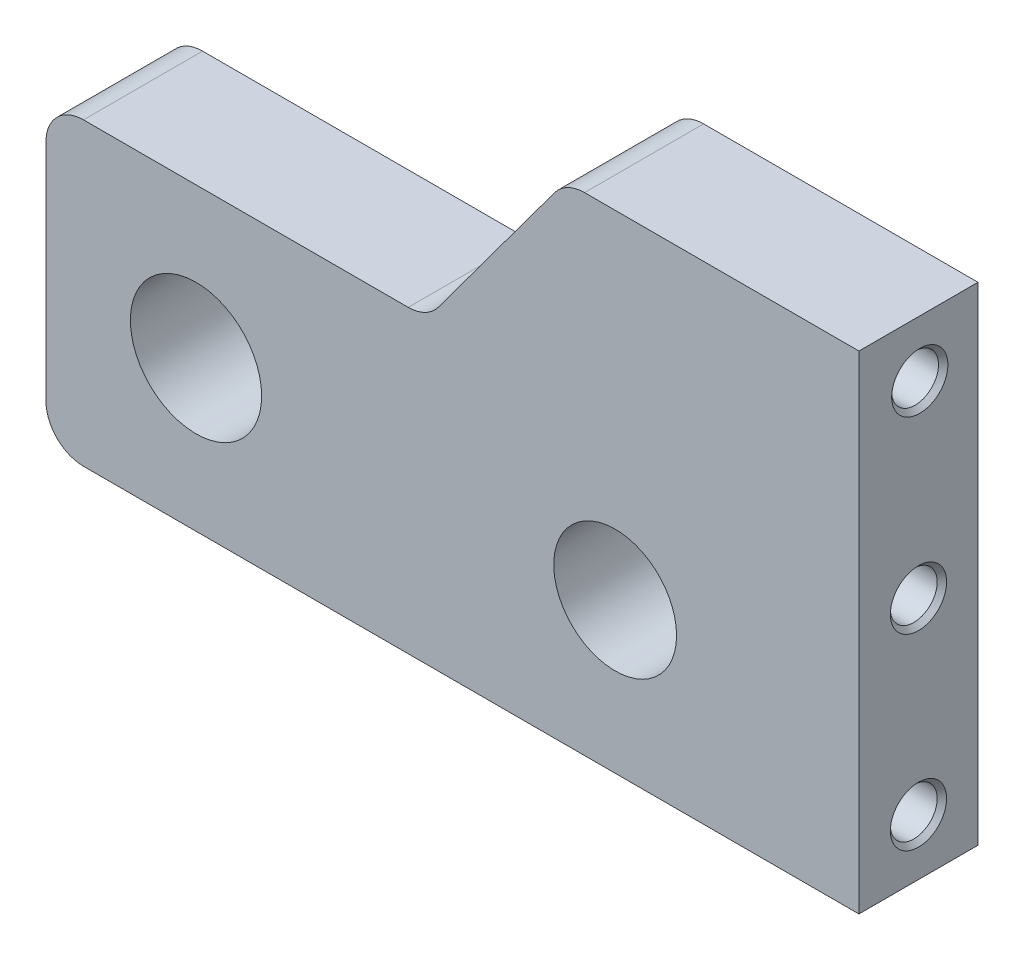
SolidWorks part; units mm, degrees
ref_plane "Front Plane" through (0, 0, 0) normal (0, 0, 1) x (1, 0, 0)
ref_plane "Top Plane" through (0, 0, 0) normal (0, 1, 0) x (1, 0, 0)
ref_plane "Right Plane" through (0, 0, 0) normal (1, 0, 0) x (0, 0, -1)
sketch "Sketch1" plane through (0, 0, 0) normal (0, 0, 1) x (1, 0, 0)
  line L0 (43.352, 8) -> (0, 8) construction
  line L1 (0, 0) -> (43.352, 0)
  line L2 (0, 0) -> (0, 16)
  line L3 (0, 16) -> (43.352, 16)
  line L4 (43.352, 0) -> (43.352, 16)
  circle A0 centre (8, 8) radius 3.5
  circle A1 centre (30.352, 8) radius 3.275
  dimension "D5" = 7
  dimension "D6" = 6.55
  dimension "D1" = 13
  dimension "D2" = 16
  dimension "D3" = 22.352
  dimension "D4" = 8
extrude "Boss-Extrude1" add sketch "Sketch1" along normal blind 6.35 contours L3 L4 L1 L2
extrude "Cut-Extrude1" cut sketch "Sketch1<6>" along normal blind 6.35 contours A0 L0 | L0 A0 | A1 region at (8, 6.5146, 0) region at (8, 9.4854, 0)
sketch "Sketch1<6>" plane through (0, 0, 0) normal (0, 0, 1) x (1, 0, 0) same geometry as "Sketch1"
fillet "Fillet1" radius 2 2 edges at (0, 16, 3.175) (0, 0, 3.175)
sketch "Sketch2" plane through (43.352, 0, 0) normal (1, 0, 0) x (0, 0, -1)
  line L0 (-6.35, 16) -> (0, 16) construction
  line L1 (-6.35, 0) -> (0, 0) construction
  line L4 (-6.35, 0) -> (-6.35, 16) construction
  circle A0 centre (-3.175, 13) radius 1.25
  circle A1 centre (-3.175, 3) radius 1.25
  dimension "D1" = 2.5
  dimension "D2" = 2.5
  dimension "D3" = 3
  dimension "D4" = 3
  dimension "D5" = 3.175
  dimension "D6" = 3.175
extrude "Cut-Extrude2" cut sketch "Sketch2" against normal blind 5
sketch "Sketch3" plane through (0, 0, 6.35) normal (0, 0, 1) x (1, 0, 0)
  line L0 (27.712, 26) -> (20.3263, 16)
  line L1 (43.352, 16) -> (27.712, 16)
  line L2 (43.352, 16) -> (43.352, 26)
  line L3 (43.352, 26) -> (27.712, 26)
  line L4 (27.712, 16) -> (27.712, 26)
  line L5 (2, 16) -> (43.352, 16) construction
  line M4 (43.352, 16) -> (2, 16)
  dimension "D1" = 10
extrude "Boss-Extrude2" add sketch "Sketch3" against normal blind 6.35 contours L4 L0 M4 | L4 L1 L2 L3 region at (25.2501, 19.3333, 6.35)
fillet "Fillet2" radius 2 2 edges at (20.3263, 16, 3.175) (27.712, 26, 3.175)
sketch "Sketch4" plane through (43.352, 0, 0) normal (1, 0, 0) x (0, 0, -1)
  line L0 (0, 26) -> (-6.35, 26) construction
  circle A0 centre (-3.1057, 23) radius 1.25
  dimension "D2" = 2.5
  dimension "D1" = 3
extrude "Cut-Extrude3" cut sketch "Sketch4" against normal blind 5
chamfer "Chamfer1" distance 0.25 angle 45 3 edges at (43.352, 3, 1.925) (43.352, 13, 1.925) (43.352, 23, 1.8557)
